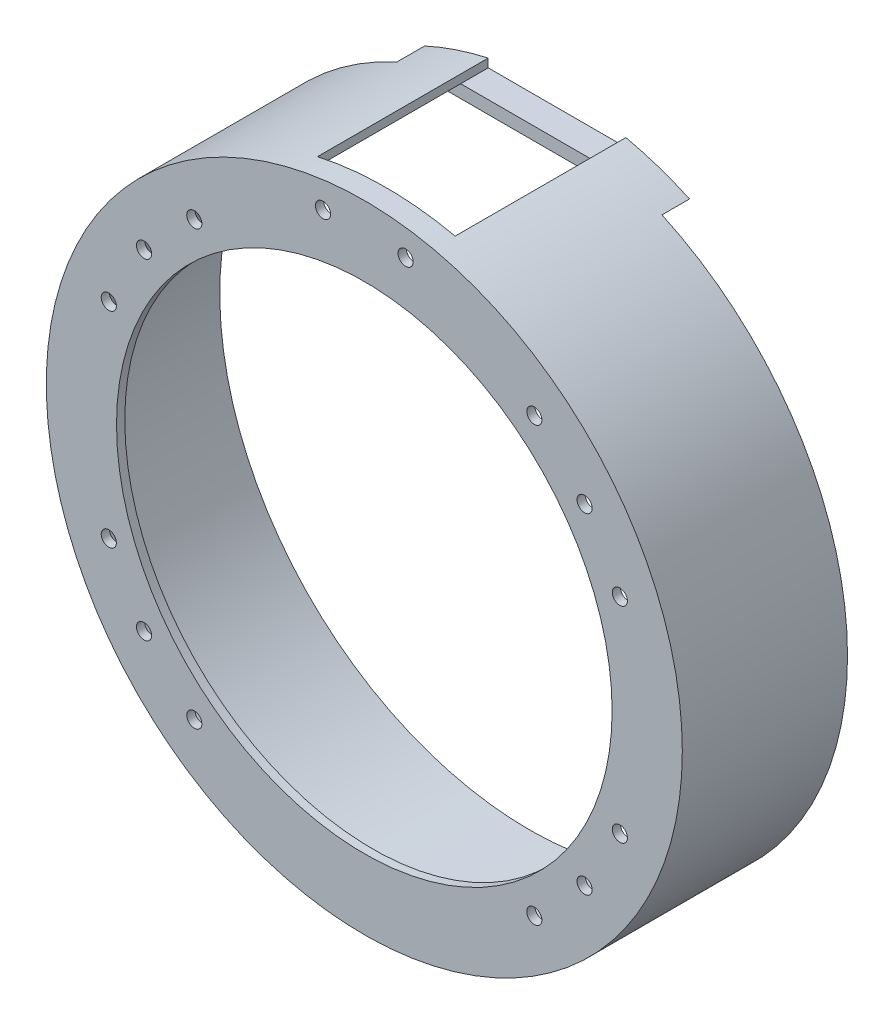
SolidWorks part; units mm, degrees
ref_plane "前视基准面" through (0, 0, 0) normal (0, 0, 1) x (1, 0, 0)
ref_plane "上视基准面" through (0, 0, 0) normal (0, 1, 0) x (1, 0, 0)
ref_plane "右视基准面" through (0, 0, 0) normal (1, 0, 0) x (0, 0, -1)
sketch "草图1" plane through (0, 0, 0) normal (0, 0, 1) x (1, 0, 0)
  circle A0 centre (0, 0) radius 112.5
  circle A1 centre (0, 0) radius 90
  dimension "D1" = 225
  dimension "D2" = 180
extrude "凸台-拉伸1" add sketch "草图1" along normal blind 3
sketch "草图4" plane through (0, 0, 3) normal (0, 0, 1) x (1, 0, 0)
  line L0 (-25, 109.6871) -> (-25, 112.7619)
  line L1 (25, 109.6871) -> (25, 112.7619)
  line L2 (0, 136.9704) -> (0, -33.2036) construction
  arc A0 (-25, 112.7619) -> (25, 112.7619) centre (0, 0) ccw
  circle A1 centre (0, 0) radius 112.5 construction
  arc A2 (-25, 109.6871) -> (25, 109.6871) centre (0, 0) ccw
  point P7 (0, 112.5)
  point P8 (25, 109.6871)
  dimension "D1" = 3
  dimension "D2" = 50
  dimension "D3" = 25
extrude "凸台-拉伸2" add sketch "草图4" against normal blind 60
sketch "草图5" plane through (0, 0, 3) normal (0, 0, 1) x (1, 0, 0)
  line L0 (0, 126.8072) -> (0, -129.5083) construction
  line L1 (-20.8005, 60) -> (139.1374, 60) construction
  line L2 (0, 0) -> (146.0961, 0) construction
  circle A0 centre (80, 60) radius 2.75
  circle A1 centre (92.8032, 37.25) radius 2.75
  circle A2 centre (61.7449, 78.6611) radius 2.75
  circle A3 centre (61.7449, -78.6611) radius 2.75
  circle A4 centre (92.8032, -37.25) radius 2.75
  circle A5 centre (80, -60) radius 2.75
  circle A6 centre (-80, -60) radius 2.75
  circle A7 centre (-92.8032, -37.25) radius 2.75
  circle A8 centre (-61.7449, -78.6611) radius 2.75
  circle A9 centre (-61.7449, 78.6611) radius 2.75
  circle A10 centre (-92.8032, 37.25) radius 2.75
  circle A11 centre (-80, 60) radius 2.75
  circle A12 centre (15, 105) radius 2.75
  circle A13 centre (-15, 105) radius 2.75
  point P13 (0, 0)
  point P16 (0, 0)
  dimension "D2" = 5.5
  dimension "D7" = 5.5
  dimension "D1" = 80
  dimension "D3" = 60
  dimension "D4" = 2
  dimension "D6" = 105
  dimension "D8" = 15
  dimension "D5" = 2
extrude "切除-拉伸1" cut sketch "草图5" against normal blind 10
sketch "草图6" plane through (0, 0, 0) normal (0, 0, -1) x (-1, 0, 0)
  circle A0 centre (0, 0) radius 112.5
  circle A1 centre (0, 0) radius 115.5
  dimension "D1" = 225
extrude "凸台-拉伸3" add sketch "草图6" along normal blind 5 and the other way blind 3
sketch "草图7" plane through (0, 0, -57) normal (0, 0, -1) x (-1, 0, 0)
  line L0 (-48.117, 105) -> (48.117, 105)
  line L4 (-25, 112.7619) -> (-25, 109.6871)
  line L5 (25, 112.7619) -> (25, 109.6871)
  line L6 (25, 109.6871) -> (25, 112.7619) construction
  line L7 (-25, 109.6871) -> (25, 109.6871)
  arc A1 (48.117, 105) -> (25, 112.7619) centre (0, 0) ccw
  arc A2 (-25, 112.7619) -> (25, 112.7619) centre (0, 0) ccw construction
  arc A3 (-25, 112.7619) -> (-48.117, 105) centre (0, 0) ccw
  dimension "D1" = 105
extrude "凸台-拉伸4" add sketch "草图7" along normal blind 10
